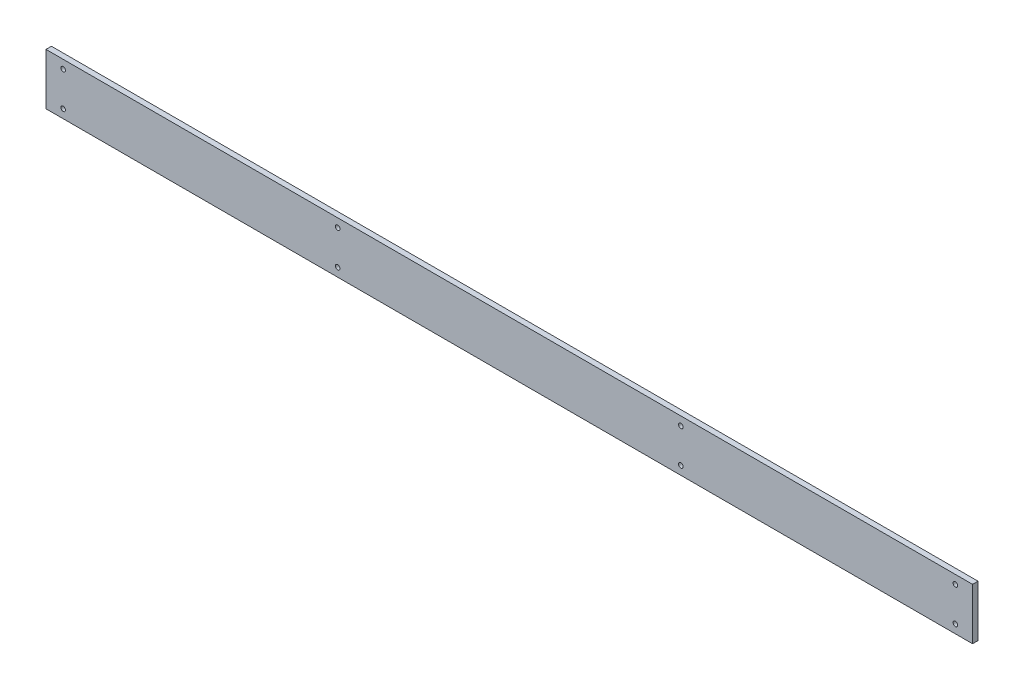
SolidWorks part; units mm, degrees
material "ABS PC"
ref_plane "Front Plane" through (0, 0, 0) normal (0, 0, 1) x (1, 0, 0)
ref_plane "Top Plane" through (0, 0, 0) normal (0, 1, 0) x (1, 0, 0)
ref_plane "Right Plane" through (0, 0, 0) normal (1, 0, 0) x (0, 0, -1)
sketch "Sketch3" plane through (0, 0, 0) normal (0, 0, 1) x (1, 0, 0)
  line L1 (-270, 15) -> (270, 15)
  line L2 (-270, 15) -> (-270, -15)
  line L3 (-270, -15) -> (270, -15)
  line L4 (270, 15) -> (270, -15)
  line L5 (-270, 15) -> (270, -15) construction
  line L6 (-270, -15) -> (270, 15) construction
  point P0 (0, 0)
  dimension "D1" = 540
  dimension "D2" = 30
extrude "Boss-Extrude3" add sketch "Sketch3" along normal blind 3.18
sketch "Sketch4" plane through (0, 0, 3.18) normal (0, 0, 1) x (1, 0, 0)
  line L0 (270, 0) -> (-270, 0) construction
  line L1 (270, -15) -> (270, 15) construction
  line L2 (-270, 15) -> (-270, -15) construction
  line L3 (0, 15) -> (0, 0) construction
  line L4 (270, 15) -> (-270, 15) construction
  line L5 (0, 0) -> (0, -15) construction
  line L6 (-270, -15) -> (270, -15) construction
  line L7 (270, 15) -> (270, 0) construction
  line L8 (270, 0) -> (270, -15) construction
  line L9 (260, 15) -> (260, 0) construction
  line L12 (260, 10) -> (270, 10) construction
  circle A0 centre (260, 10) radius 1.35
  dimension "D2" = 2.7
  dimension "D3" = 10
  dimension "D1" = 5
extrude "Cut-Extrude1" cut sketch "Sketch4" against normal up to next
mirror "Mirror1" about plane through (0, 0, 0) normal (0, 1, 0) of "Cut-Extrude1"
mirror "Mirror2" about plane through (0, 0, 0) normal (1, 0, 0) of "Mirror1"
sketch "Sketch5" plane through (0, 0, 3.18) normal (0, 0, 1) x (1, 0, 0)
  line L0 (0, -10) -> (100, -10) construction
  line L1 (-270, -15) -> (270, -15) construction
  circle A0 centre (100, -10) radius 1.35
  dimension "D2" = 2.7
  dimension "D1" = 100
  dimension "D3" = 5
extrude "Cut-Extrude2" cut sketch "Sketch5" against normal up to next
mirror "Mirror3" about plane through (0, 0, 0) normal (1, 0, 0) of "Cut-Extrude2"
mirror "Mirror4" about plane through (0, 0, 0) normal (0, 1, 0) of "Mirror3", "Cut-Extrude2"
